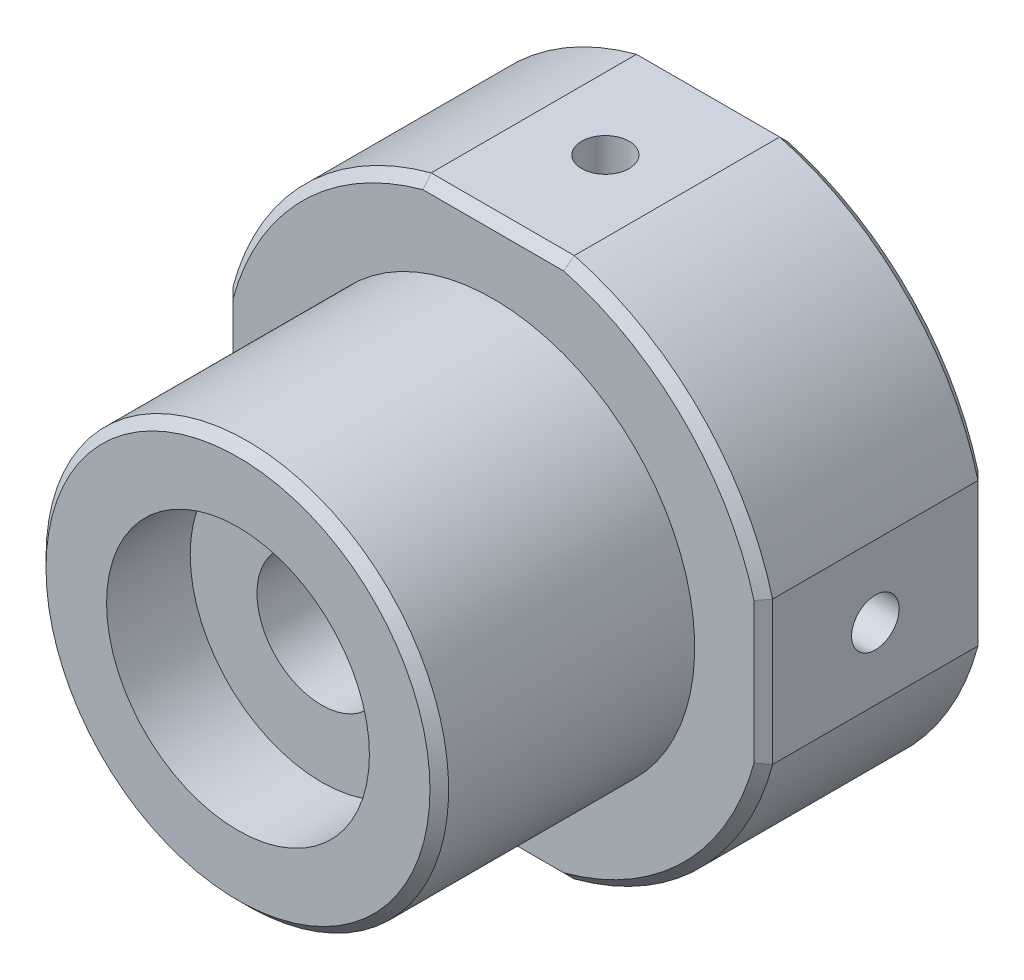
SolidWorks part; units mm, degrees
ref_plane "Front Plane" through (0, 0, 0) normal (0, 0, 1) x (1, 0, 0)
ref_plane "Top Plane" through (0, 0, 0) normal (0, 1, 0) x (1, 0, 0)
ref_plane "Right Plane" through (0, 0, 0) normal (1, 0, 0) x (0, 0, -1)
sketch "Sketch1" plane through (0, 0, 0) normal (0, 0, 1) x (1, 0, 0)
  line L0 (-6.0886, 22.9552) -> (6.0886, 22.9552)
  line L1 (-34.6679, 0) -> (42.0872, 0) construction
  line L2 (22.9553, 6.0886) -> (22.9552, -6.0886)
  line L3 (6.0886, -22.9553) -> (-6.0886, -22.9552)
  line L4 (-22.9553, -6.0886) -> (-22.9552, 6.0886)
  circle A0 centre (0, 0) radius 23.749
  point P16 (0, 0)
  dimension "D1" = 47.498
  dimension "D2" = 0.7937
  dimension "D4" = 22.9552
  dimension "D3" = 4
extrude "Boss-Extrude1" add sketch "Sketch1" along normal mid plane 19.05 contours L4 L1 L2 A0 L0 | L1 L4 A0 L3 L2 region at (0, 10.0394, 0) region at (0, -10.0394, 0)
sketch "Sketch2" plane through (0, 0, -9.525) normal (0, 0, -1) x (-1, 0, 0)
  circle A0 centre (0, 0) radius 11.176
  circle A1 centre (0, 0) radius 5.5004
  dimension "D1" = 22.352
  dimension "D2" = 11.0007
extrude "Cut-Extrude1" cut sketch "Sketch2" against normal blind 7.112 contours A1 | A0 A1 | A0 region at (10.8599, 0, -9.525) region at (0, 0, -9.525)
sketch "Sketch3" plane through (0, 0, 9.525) normal (0, 0, 1) x (1, 0, 0)
  circle A0 centre (0, 0) radius 17.1196
  dimension "D1" = 34.2392
extrude "Boss-Extrude2" add sketch "Sketch3" along normal blind 21.717
extrude "Cut-Extrude2" cut sketch "Sketch2<3>" against normal through all contours A1 region at (0, 0, -9.525)
sketch "Sketch2<3>" plane through (0, 0, -9.525) normal (0, 0, -1) x (-1, 0, 0) same geometry as "Sketch2"
sketch "Sketch4" plane through (0, 0, 31.242) normal (0, 0, 1) x (1, 0, 0)
  circle A0 centre (0, 0) radius 11.176
  dimension "D1" = 22.352
extrude "Cut-Extrude3" cut sketch "Sketch4" against normal blind 7.112
sketch "Sketch5" plane through (-22.9552, 0, 0) normal (-1, 0, 0) x (0, 0, 1)
  point P0 (0, 0)
hole_wizard "#10-32 Tapped Hole1" positions "3DSketch1" profile "Sketch7" tap size "#10-32" standard "ANSI Inch"
sketch3d "3DSketch1"
  point P0 (-22.9552, 0, 0)
sketch "Sketch7" plane through (-22.9552, 0, 0) normal (0, 1, 0) x (0, 0, 1)
  line L0 (0, 0) -> (0, 12.065)
  line L1 (0, 12.065) -> (2.0193, 10.8517)
  line L2 (2.0193, 10.8517) -> (2.0193, 0)
  line L5 (2.0193, 0) -> (0, 0)
  line L10 (0, 12.065) -> (-2.0193, 10.8517) construction
  line L11 (0, -6.35) -> (0, 107.95) construction
  dimension "Tap Drill Dia." = 4.0386
  dimension "Tap Drill Depth" = 12.065
  dimension "Drill Angle" = 118
pattern_circular "CirPattern1" count 4 every 90 about axis through (0, 0, 31.242) along (0, 0, 1) of "#10-32 Tapped Hole1"
chamfer "Chamfer2" distance 0.7937 angle 45 17 edges at (16.7931, 16.7931, -9.525) (22.9552, 0, -9.525) (16.7931, -16.7931, -9.525) (0, -22.9552, -9.525) (-16.7931, -16.7931, -9.525) (-22.9552, 0, -9.525) (-16.7931, 16.7931, -9.525) (0, 22.9552, -9.525) (17.1196, 0, 31.242) (-16.7931, 16.7931, 9.525) (-22.9552, 0, 9.525) (-16.7931, -16.7931, 9.525) (0, -22.9552, 9.525) (16.7931, -16.7931, 9.525) (22.9552, 0, 9.525) (16.7931, 16.7931, 9.525) (0, 22.9552, 9.525)
sketch "Sketch8" plane through (0, 0, -9.525) normal (0, 0, -1) x (-1, 0, 0)
  line L0 (0, 0) -> (-26.7754, 0) construction
  line L1 (0, -29.716) -> (0, 29.716) construction
  line L2 (0, 0) -> (-22.1615, 5.9843) construction
  line L3 (0, 0) -> (-5.9843, 22.1615) construction
  line L4 (-19.0963, 5.1566) -> (-11.0808, 2.9921)
  line L5 (-5.1566, 19.0963) -> (-2.9921, 11.0807)
  line L6 (5.1566, 19.0963) -> (2.9921, 11.0808)
  line L7 (19.0963, 5.1566) -> (11.0808, 2.9921)
  line L8 (19.0963, -5.1566) -> (11.0807, -2.9921)
  line L9 (5.1566, -19.0963) -> (2.9921, -11.0808)
  line L10 (-5.1566, -19.0963) -> (-2.9921, -11.0807)
  line L11 (-19.0963, -5.1566) -> (-11.0808, -2.9921)
  circle A0 centre (0, 0) radius 11.176 construction
  circle A1 centre (0, 0) radius 11.176
  arc A3 (19.0963, 5.1566) -> (5.1566, 19.0963) centre (0, 0) ccw
  arc A4 (-5.1566, 19.0963) -> (-19.0963, 5.1566) centre (0, 0) ccw
  arc A5 (-5.1566, 19.0963) -> (-19.0963, 5.1566) centre (0, 0) ccw
  arc A6 (5.1566, -19.0963) -> (19.0963, -5.1566) centre (0, 0) ccw
  arc A7 (-19.0963, -5.1566) -> (-5.1566, -19.0963) centre (0, 0) ccw
  circle A8 centre (0, 0) radius 14.351
  point P4 (0, 0)
  point P34 (0, 0)
  dimension "D1" = 3.175
  dimension "D3" = 3.175
  dimension "D2" = 4
extrude "Cut-Extrude4" cut sketch "Sketch8" against normal blind 12.7 contours A8 L11 A7 L10 | A8 L9 A6 L8 | A8 L7 A3 L6 | A8 L5 A5 L4 region at (11.6245, 11.6245, -9.525) region at (11.6245, -11.6245, -9.525) region at (-11.6245, 11.6245, -9.525) region at (-11.6245, -11.6245, -9.525)
fillet "Fillet2" radius 3.429 16 edges at (-5.1566, -19.0963, -3.175) (-19.0963, 5.1566, -3.175) (-5.1566, 19.0963, -3.175) (-13.8548, -3.7412, -3.175) (-19.0963, -5.1566, -3.175) (-3.7412, -13.8548, -3.175) (5.1566, -19.0963, -3.175) (3.7412, -13.8548, -3.175) (19.0963, -5.1566, -3.175) (13.8548, -3.7412, -3.175) (13.8548, 3.7412, -3.175) (19.0963, 5.1566, -3.175) (3.7412, 13.8548, -3.175) (5.1566, 19.0963, -3.175) (-13.8548, 3.7412, -3.175) (-3.7412, 13.8548, -3.175)
